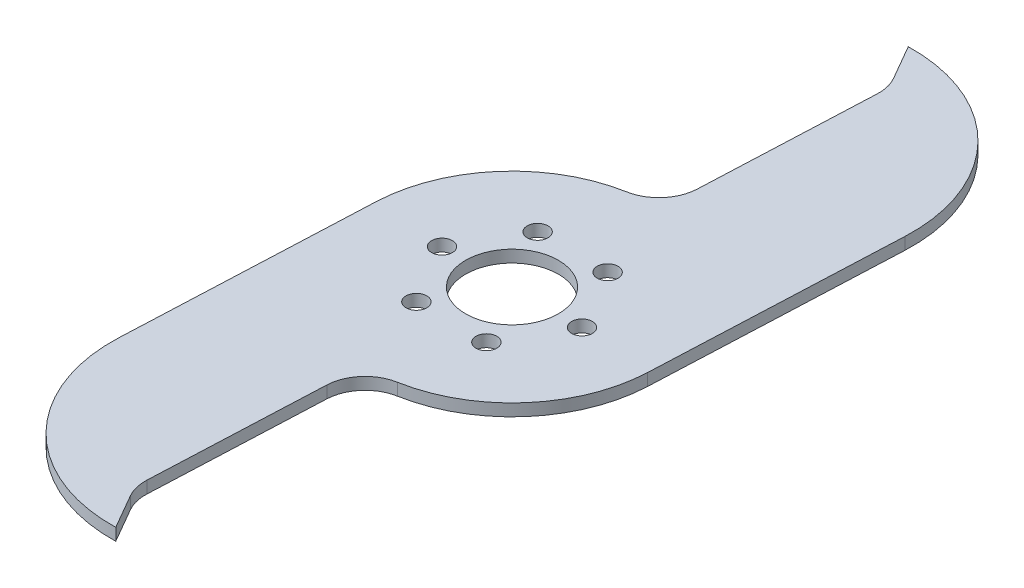
SolidWorks part; units mm, degrees
ref_plane "Front Plane" through (0, 0, 0) normal (0, 0, 1) x (1, 0, 0)
ref_plane "Top Plane" through (0, 0, 0) normal (0, 1, 0) x (1, 0, 0)
ref_plane "Right Plane" through (0, 0, 0) normal (1, 0, 0) x (0, 0, -1)
ref_axis "Axis1" through (0, -0.15, 0) along (0, 1, 0)
sketch "Sketch1" plane through (0, 0, 0) normal (0, 1, 0) x (1, 0, 0)
  line L1 (17.5, 0) -> (8.75, 15.1554) construction
  line L2 (8.75, 15.1554) -> (-8.75, 15.1554) construction
  line L3 (-8.75, 15.1554) -> (-17.5, 0) construction
  line L4 (-17.5, 0) -> (-8.75, -15.1554) construction
  line L5 (-8.75, -15.1554) -> (8.75, -15.1554) construction
  line L6 (8.75, -15.1554) -> (17.5, 0) construction
  circle A0 centre (0, 0) radius 15.1554 construction
  circle A1 centre (8.75, 15.1554) radius 2.6
  circle A2 centre (17.5, 0) radius 2.6
  circle A3 centre (8.75, -15.1554) radius 2.6
  circle A4 centre (-8.75, -15.1554) radius 2.6
  circle A5 centre (-17.5, 0) radius 2.6
  circle A6 centre (-8.75, 15.1554) radius 2.6
  circle A7 centre (0, 0) radius 11.6
  circle A8 centre (0, 0) radius 101.6 construction
  dimension "D1" = 5.2
  dimension "D2" = 23.2
  dimension "D3" = 203.2
  dimension "D4" = 35
sketch "Sketch2" plane through (0, 0, 0) normal (0, 1, 0) x (1, 0, 0)
  line L0 (0, -1000) -> (0, 49000) construction
  line L1 (-2.5, 101.5692) -> (2.5, 92.909)
  line L2 (0, 0) -> (35355.3391, 35355.3391) construction
  line L3 (3.8302, 87.4715) -> (1.9418, 44.345)
  line L4 (-1000, 0) -> (49000, 0) construction
  line L5 (38.1664, 60.1165) -> (35.466, -1.553)
  circle A0 centre (0, 0) radius 101.6 construction
  arc A1 (-2.5, 101.5692) -> (38.1664, 60.1165) centre (-1.5225, 61.8544) cw
  circle A3 centre (0, 0) radius 79.6 construction
  circle A5 centre (0, 0) radius 35.5 construction
  arc A20 (-2.5, 101.5692) -> (0, 0) centre (-49.5947, 49.5947) cw construction
  arc A21 (2.5, 92.909) -> (3.8302, 87.4715) centre (-6.1603, 87.909) cw
  arc A25 (1.9418, 44.345) -> (-6.2797, 34.9402) centre (-8.0487, 44.7825) cw
  arc A26 (-6.2797, 34.9402) -> (35.466, -1.553) centre (0, 0) ccw
  point P7 (0, 97.2391)
  point P11 (40.5895, 55.6237)
  point P16 (-79.6, 0)
  point P17 (-101.6, 0)
  point P21 (35.5, 0)
  dimension "D3" = 45
  dimension "D7" = 10
  dimension "D1" = 30
  dimension "D2" = 22
  dimension "D4" = 10
  dimension "D5" = 18
  dimension "D6" = 35.5
extrude "Boss-Extrude1" add sketch "Sketch2" along normal blind 3.02
pattern_circular "CirPattern1" count 2 over 360 about axis through (0, -0.15, 0) along (0, 1, 0) of bodies 101
combine bodies "Combine1" bodies to combine 101 102
extrude "Cut-Extrude3" cut sketch "Sketch1" along normal through all
